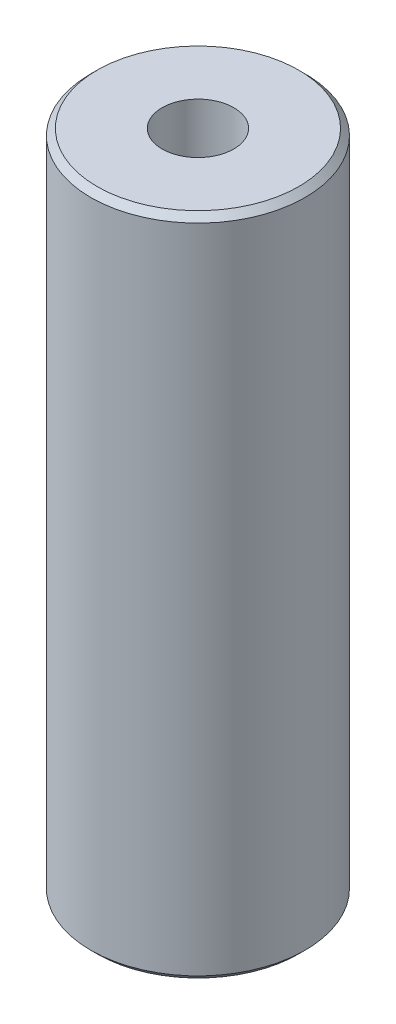
SolidWorks part; units mm, degrees
ref_plane "Front Plane" through (0, 0, 0) normal (0, 0, 1) x (1, 0, 0)
ref_plane "Top Plane" through (0, 0, 0) normal (0, 1, 0) x (1, 0, 0)
ref_plane "Right Plane" through (0, 0, 0) normal (1, 0, 0) x (0, 0, -1)
sketch "Sketch1" plane through (0, 0, 0) normal (0, 1, 0) x (1, 0, 0)
  circle A0 centre (0, 0) radius 52.5
  dimension "SHAFT_OD" = 105
extrude "Boss-Extrude1" add sketch "Sketch1" along normal blind 325.5466
sketch "Sketch2" plane through (0, 0, 0) normal (0, 1, 0) x (1, 0, 0)
  circle A0 centre (0, 0) radius 17.5555
  dimension "BORE_D" = 35.111
extrude "Cut-Extrude1" cut sketch "Sketch2" along normal through all
chamfer "Chamfer1" distance 3.0926 angle 45 2 edges at (0, 325.5466, 52.5) (0, 0, 52.5)
